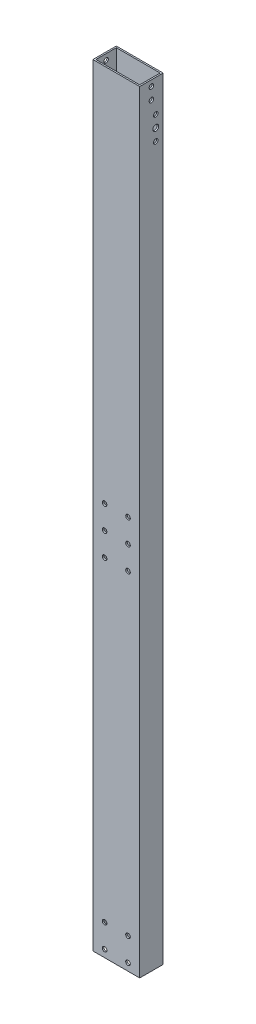
SolidWorks part; units mm, degrees
material "6061-T6 (SS)"
ref_plane "Front Plane" through (0, 0, 0) normal (0, 0, 1) x (1, 0, 0)
ref_plane "Top Plane" through (0, 0, 0) normal (0, 1, 0) x (1, 0, 0)
ref_plane "Right Plane" through (0, 0, 0) normal (1, 0, 0) x (0, 0, -1)
sketch "Sketch1" plane through (0, 0, 0) normal (0, 0, 1) x (1, 0, 0)
  line L1 (-25.4, -419.1) -> (25.4, -419.1)
  line L2 (-25.4, -419.1) -> (-25.4, 419.1)
  line L3 (-25.4, 419.1) -> (25.4, 419.1)
  line L4 (25.4, -419.1) -> (25.4, 419.1)
  line L5 (-25.4, -419.1) -> (25.4, 419.1) construction
  line L6 (-25.4, 419.1) -> (25.4, -419.1) construction
  point P0 (0, 0)
  dimension "D1" = 50.8
  dimension "D2" = 838.2
extrude "Boss-Extrude1" add sketch "Sketch1" along normal mid plane 25.4
shell "Shell1" thickness 1.5875 removed face at (0, -419.1, 0) removed face at (0, 419.1, 0)
sketch "Sketch3" plane through (0, 0, 0) normal (1, 0, 0) x (0, 0, -1)
  line L0 (-12.7, -419.1) -> (12.7, -419.1) construction
  line L1 (-12.7, 419.1) -> (12.7, 419.1) construction
  circle A0 centre (0, 400.05) radius 2.4892
  circle A1 centre (0, 412.75) radius 2.4892
  point P6 (0, -419.1)
  dimension "D1" = 4.9784
  dimension "D2" = 6.35
  dimension "D3" = 12.7
extrude "Cut-Extrude1" cut sketch "Sketch3" against normal through all both and the other way through all
sketch "Sketch4" plane through (0, 0, 0) normal (1, 0, 0) x (0, 0, -1)
  line L0 (12.7, 419.1) -> (12.7, -419.1) construction
  line L3 (-12.7, 419.1) -> (12.7, 419.1) construction
  circle A0 centre (4.7625, 371.475) radius 3.175
  circle A1 centre (4.7625, 384.175) radius 2.4892
  circle A2 centre (4.7625, 358.775) radius 2.4892
  dimension "D1" = 6.35
  dimension "D4" = 4.9784
  dimension "D2" = 7.9375
  dimension "D5" = 12.7
  dimension "D6" = 12.7
  dimension "D3" = 47.625
extrude "Cut-Extrude2" cut sketch "Sketch4" against normal through all both and the other way through all
sketch "Sketch5" plane through (0, 0, 0) normal (0, 0, 1) x (1, 0, 0)
  line L1 (-15.875, 384.9687) -> (15.875, 384.9687)
  line L2 (-15.875, 384.9687) -> (-15.875, 357.9812)
  line L3 (-15.875, 357.9812) -> (15.875, 357.9812)
  line L4 (15.875, 384.9687) -> (15.875, 357.9812)
  line L6 (25.4, 419.1) -> (-25.4, 419.1) construction
  point P4 (-15.875, 371.475)
  point P8 (0, 384.9687)
  point P9 (0, 419.1)
  dimension "D1" = 31.75
  dimension "D2" = 26.9875
  dimension "D3" = 47.625
extrude "Cut-Extrude3" cut sketch "Sketch5" against normal through all
fillet "Fillet1" radius 3.175 4 edges at (15.875, 384.9687, -11.9062) (15.875, 357.9812, -11.9062) (-15.875, 357.9812, -11.9062) (-15.875, 384.9687, -11.9062)
sketch "Sketch6" plane through (0, 0, 0) normal (0, 0, 1) x (1, 0, 0)
  line L0 (-25.4, 419.1) -> (-25.4, -419.1) construction
  line L1 (-25.4, -419.1) -> (25.4, -419.1) construction
  circle A0 centre (-12.7, 7.9375) radius 2.4892
  circle A1 centre (12.7, 7.9375) radius 2.4892
  circle A2 centre (12.7, -17.4625) radius 2.4892
  circle A3 centre (12.7, -42.8625) radius 2.4892
  circle A4 centre (-12.7, -17.4625) radius 2.4892
  circle A5 centre (-12.7, -42.8625) radius 2.4892
  circle A6 centre (-12.7, -411.1625) radius 2.4892
  circle A7 centre (12.7, -411.1625) radius 2.4892
  circle A8 centre (12.7, -385.7625) radius 2.4892
  circle A9 centre (-12.7, -385.7625) radius 2.4892
  point P8 (0, 0)
  point P20 (5.1022, -412.165)
  dimension "D1" = 4.9784
  dimension "D3" = 427.0375
  dimension "D7" = 25.4
  dimension "D2" = 12.7
  dimension "D6" = 25.4
  dimension "D8" = 7.9375
  dimension "D9" = 12.7
  dimension "D12" = 25.4
  dimension "D13" = 25.4
  dimension "D4" = 2
  dimension "D5" = 3
  dimension "D10" = 2
  dimension "D11" = 2
extrude "Cut-Extrude4" cut sketch "Sketch6" along normal through all
equation "\"D6@Sketch4\"=\"D5@Sketch4\""
